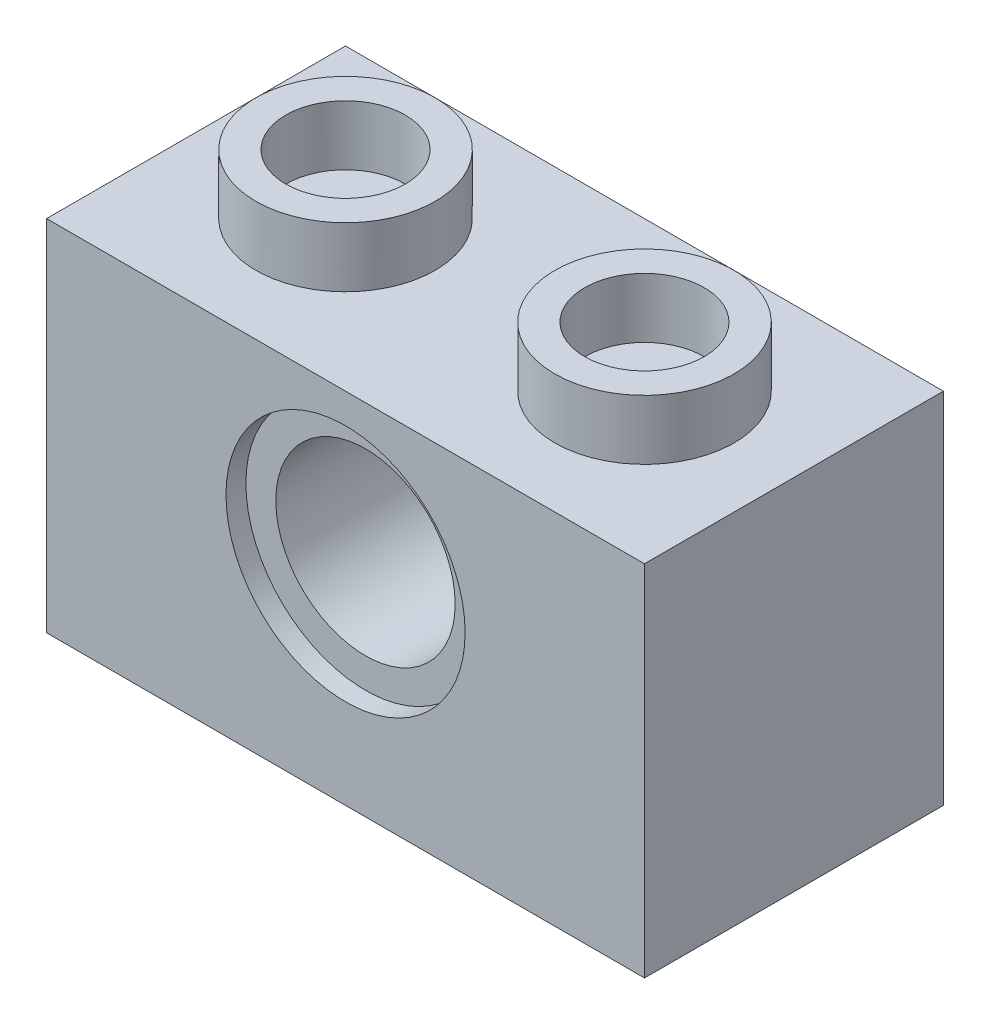
SolidWorks part; units mm, degrees
ref_plane "Front Plane" through (0, 0, 0) normal (0, 0, 1) x (1, 0, 0)
ref_plane "Top Plane" through (0, 0, 0) normal (0, 1, 0) x (1, 0, 0)
ref_plane "Right Plane" through (0, 0, 0) normal (1, 0, 0) x (0, 0, -1)
sketch "Sketch1" plane through (0, 0, 0) normal (0, 1, 0) x (1, 0, 0)
  line L1 (0, 0) -> (10, 0)
  line L2 (0, 0) -> (0, 5)
  line L3 (0, 5) -> (10, 5)
  line L4 (10, 0) -> (10, 5)
  line L5 (1, 4) -> (9, 4)
  line L6 (1, 4) -> (1, 1)
  line L7 (1, 1) -> (9, 1)
  line L8 (9, 4) -> (9, 1)
  point P9 (5, 4)
  point P10 (5, 5)
  point P11 (1, 2.5)
  point P12 (0, 2.5)
  dimension "D1" = 10
  dimension "D2" = 5
  dimension "D3" = 1
  dimension "D4" = 1
extrude "Boss-Extrude1" add sketch "Sketch1" along normal blind 6
sketch "Sketch2" plane through (1, 0, 0) normal (1, 0, 0) x (0, 0, -1)
  line L0 (1, 6) -> (1, 0) construction
  line L1 (4, 6) -> (1, 6)
  line L2 (4, 6) -> (4, 5)
  line L3 (4, 5) -> (1, 5)
  line L4 (1, 6) -> (1, 5)
  dimension "D1" = 1
extrude "Boss-Extrude2" add sketch "Sketch2" along normal up to next
sketch "Sketch4" plane through (0, 6, 0) normal (0, 1, 0) x (1, 0, 0)
  line L0 (0, 5) -> (0, 0) construction
  line L1 (0, 2.5) -> (10, 2.5)
  line L2 (10, 0) -> (10, 5) construction
  line L3 (5, 5) -> (5, 0)
  line L4 (10, 5) -> (0, 5) construction
  line L5 (0, 0) -> (10, 0) construction
  circle A0 centre (2.5, 2.5) radius 1.5
  circle A1 centre (7.5, 2.5) radius 1.5
  circle A2 centre (7.5, 2.5) radius 1
  circle A3 centre (2.5, 2.5) radius 1
  dimension "D2" = 3
  dimension "D3" = 2
  dimension "D1" = 2.5
extrude "Boss-Extrude3" add sketch "Sketch4" along normal blind 1 contours L1 A0 | L1 A0 | A1 L1 | A1 L1 region at (2.5, 6, -3.5335) region at (3.75, 6, -2.4665) region at (7.5, 6, -3.9665) region at (6.25, 6, -2.4665)
sketch "Sketch6" plane through (0, 5, 0) normal (0, -1, 0) x (-1, 0, 0)
  line L0 (-1, 2.5) -> (-9, 2.5)
  line L1 (-1, 1) -> (-1, 4) construction
  line L2 (-9, 4) -> (-9, 1) construction
  circle A0 centre (-2.5, 2.5) radius 0.75
  circle A1 centre (-2.5, 2.5) radius 1.5
  circle A2 centre (-5, 2.5) radius 1
extrude "Boss-Extrude4" add sketch "Sketch6" along normal up to surface (5 mm away) contours L0 A2 | L0 A2 region at (5, 5, -2.0756) region at (5, 5, -2.9244) up to face at (5, 0, -2.5)
sketch "Sketch7" plane through (0, 0, -5) normal (0, 0, -1) x (-1, 0, 0)
  line L0 (-5, 0) -> (-5, 6)
  line L1 (-10, 0) -> (0, 0) construction
  line L2 (-10, 6) -> (0, 6) construction
  circle A0 centre (-5, 3.5) radius 1.5
  circle A1 centre (-5, 3.5) radius 2
  dimension "D1" = 3
  dimension "D3" = 4
  dimension "D2" = 2.5
extrude "Boss-Extrude5" add sketch "Sketch7" against normal up to surface (5 mm away) contours L0 A1 A0 | L0 A1 A0 | L0 A0 | L0 A0 region at (6.9553, 3.5, -5) region at (4.9553, 1.75, -5) region at (5.6366, 3.5, -5) region at (4.3634, 3.5, -5) up to face at (5, 3, 0)
extrude "Cut-Extrude2" cut sketch "Sketch7<3>" against normal up to surface (5 mm away) contours L0 A0 | L0 A0 region at (5.6366, 3.5, -5) region at (4.3634, 3.5, -5) up to face at (5, 3, 0)
sketch "Sketch7<3>" plane through (0, 0, -5) normal (0, 0, -1) x (-1, 0, 0) same geometry as "Sketch7"
extrude "Cut-Extrude3" cut sketch "Sketch7<4>" against normal blind 0.3333 contours L0 A1 A0 | L0 A1 A0 region at (6.9553, 3.5, -5) region at (4.9553, 1.75, -5)
sketch "Sketch7<4>" plane through (0, 0, -5) normal (0, 0, -1) x (-1, 0, 0) same geometry as "Sketch7"
sketch "Sketch8" plane through (0, 0, 0) normal (0, 0, 1) x (1, 0, 0)
  circle A0 centre (5, 3.5) radius 2
  dimension "D1" = 4
extrude "Cut-Extrude4" cut sketch "Sketch8" against normal blind 0.3333
